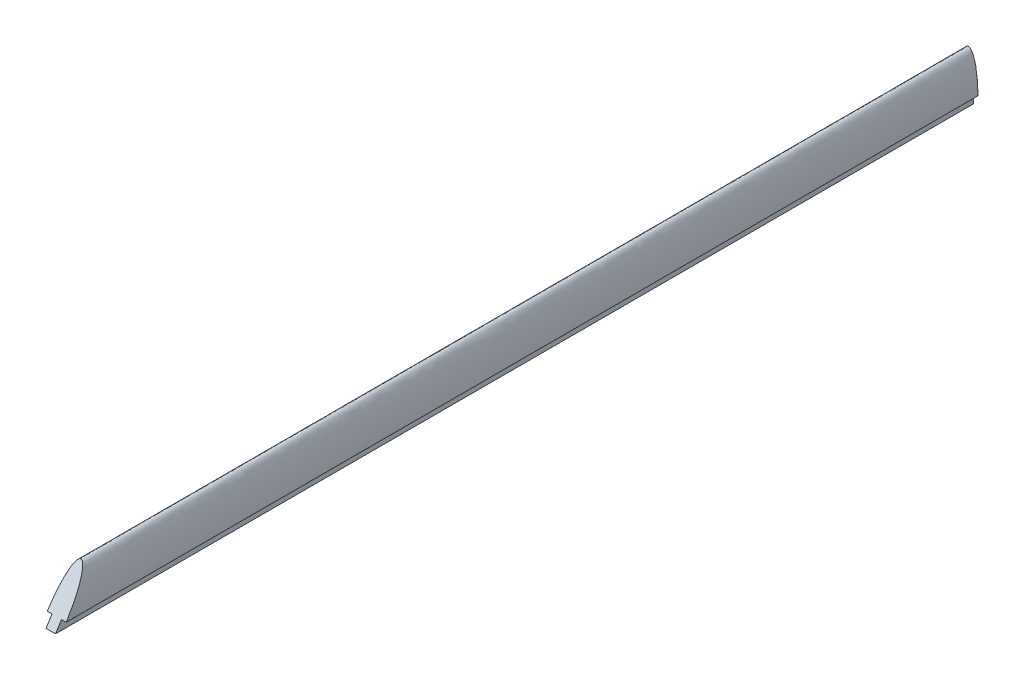
SolidWorks part; units mm, degrees
ref_plane "Front Plane" through (0, 0, 0) normal (0, 0, 1) x (1, 0, 0)
ref_plane "Top Plane" through (0, 0, 0) normal (0, 1, 0) x (1, 0, 0)
ref_plane "Right Plane" through (0, 0, 0) normal (1, 0, 0) x (0, 0, -1)
sketch "Cross Section" plane through (0, 0, 0) normal (0, 0, 1) x (1, 0, 0)
  line L0 (10, 0) -> (20, 0) construction
  line L1 (0, 80) -> (0, 0) construction
  line L2 (10, 0) -> (20, 0)
  line L4 (-10, 0) -> (-10, -20)
  line L5 (-10, -20) -> (10, -20)
  line L6 (10, 0) -> (10, -20)
  line L7 (-10, 0) -> (10, -20) construction
  line L8 (-10, -20) -> (10, 0) construction
  line L10 (-20, 0) -> (-10, 0)
  line L11 (-10, 0) -> (10, 0) construction
  ellipse E0 centre (0, 0) end of major axis (0, -80) minor radius 20 (20, 0) -> (-20, 0) ccw
  point P2 (0, -10)
  dimension "D1" = 40
  dimension "D2" = 80
  dimension "D3" = 10
extrude "Profile Extrude" add sketch "Cross Section" along normal blind 2000
sketch "Flush Support Cut Sketch" plane through (0, 0, 0) normal (1, 0, 0) x (0, 0, -1)
  line L0 (-2000, -126.1238) -> (-1869.2562, 80)
  line L1 (-1869.2562, 80) -> (-2000, 80)
  line L2 (-2000, 80) -> (-2000, -126.1238)
  line L3 (-2000, 80) -> (-2000, 0) construction
  line L4 (0, 80) -> (-2000, 80) construction
  line L5 (-1920, 0) -> (-1989.8893, -110.1839) construction
  point P10 (0, 0)
extrude "Flush Support Cut" cut sketch "Flush Support Cut Sketch" against normal up to surface and the other way up to surface up to face at (0, 40, 1000) other way up to face at (0, 40, 1000)
